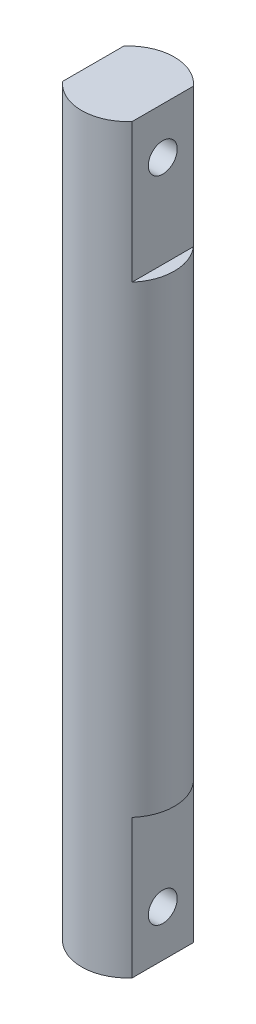
SolidWorks part; units mm, degrees
ref_plane "前视基准面" through (0, 0, 0) normal (0, 0, 1) x (1, 0, 0)
ref_plane "上视基准面" through (0, 0, 0) normal (0, 1, 0) x (1, 0, 0)
ref_plane "右视基准面" through (0, 0, 0) normal (1, 0, 0) x (0, 0, -1)
other "Configuration Table"
sketch "草图1" plane through (0, 0, 0) normal (0, 1, 0) x (1, 0, 0)
  circle A0 centre (0, 0) radius 4
  dimension "D1" = 8
extrude "凸台-拉伸1" add sketch "草图1" along normal blind 32 and the other way blind 32
ref_plane "基准面1" through (10, 0, 0) normal (1, 0, 0) x (0, 0, -1)
sketch "草图7" plane through (10, 0, 0) normal (1, 0, 0) x (0, 0, -1)
  circle A0 centre (0, 28) radius 1.25
  circle A1 centre (0, -28) radius 1.25
  dimension "D1" = 2.5
  dimension "D2" = 2.5
  dimension "D3" = 28
  dimension "D4" = 28
sketch "草图8" plane through (10, 0, 0) normal (1, 0, 0) x (0, 0, -1)
  line L1 (-12.0569, 37.3082) -> (15.3796, 37.3082)
  line L2 (-12.0569, 37.3082) -> (-12.0569, -37.8679)
  line L3 (-12.0569, -37.8679) -> (15.3796, -37.8679)
  line L4 (15.3796, 37.3082) -> (15.3796, -37.8679)
sketch "草图17" plane through (10, 0, 0) normal (1, 0, 0) x (0, 0, -1)
  point P0 (0, 28)
  point P3 (0, -28)
hole_wizard "M3 螺纹孔2" positions "草图17" profile "草图16" tap size "M3" standard "GB" end condition through all
sketch "草图16" plane through (10, 28, 0) normal (0, 1, 0) x (0, 0, -1)
  line L0 (0, 0) -> (0, 14)
  line L1 (0, 14) -> (1.25, 14)
  line L2 (1.25, 14) -> (1.25, 0.275)
  line L3 (1.25, 0.275) -> (1.525, 0)
  line L5 (1.525, 0) -> (0, 0)
  line L6 (-1.25, 0.275) -> (-1.525, 0) construction
  line L11 (0, -6.35) -> (0, 107.95) construction
  dimension "通孔螺纹孔钻头直径" = 2.5
  dimension "通孔螺纹孔钻头深度" = 14
  dimension "近端锥形沉头孔直径" = 3.05
  dimension "近端锥形沉头孔角度" = 90
cosmetic thread "孔螺纹线3" parameters "D2"=3
cosmetic thread "孔螺纹线4" parameters "D2"=3
sketch "草图18" plane through (10, 0, 0) normal (1, 0, 0) x (0, 0, -1)
  line L1 (-17.2448, 39.0552) -> (16.0059, 39.0552)
  line L2 (-17.2448, 39.0552) -> (-17.2448, 20)
  line L3 (-17.2448, 20) -> (16.0059, 20)
  line L4 (16.0059, 39.0552) -> (16.0059, 20)
  line L5 (-23.3195, -20) -> (22.784, -20)
  line L6 (-23.3195, -20) -> (-23.3195, -55.5527)
  line L7 (-23.3195, -55.5527) -> (22.784, -55.5527)
  line L8 (22.784, -20) -> (22.784, -55.5527)
  dimension "D1" = 20
  dimension "D2" = 20
extrude "切除-拉伸1" cut sketch "草图18" against normal blind 7
sketch "草图19" plane through (0, -32, 0) normal (0, -1, 0) x (1, 0, 0)
  line L0 (0, 0) -> (0, 2.7362) construction
  line L1 (3, -2.6458) -> (3, 2.6458) construction
  line L2 (3, -2.6458) -> (3, 2.6458)
  line L3 (-3, -2.6458) -> (-3, 2.6458)
  arc A0 (3, -2.6458) -> (3, 2.6458) centre (0, 0) ccw construction
  arc A1 (3, -2.6458) -> (3, 2.6458) centre (0, 0) ccw
  arc A2 (-3, -2.6458) -> (-3, 2.6458) centre (0, 0) cw
extrude "切除-拉伸2" cut sketch "草图19" against normal blind 12
sketch "草图20" plane through (0, 32, 0) normal (0, 1, 0) x (1, 0, 0)
  line L0 (0, 0) -> (0, 5.7593) construction
  line L1 (3, -2.6458) -> (3, 2.6458) construction
  line L2 (3, -2.6458) -> (3, 2.6458)
  line L3 (-3, -2.6458) -> (-3, 2.6458)
  arc A0 (3, -2.6458) -> (3, 2.6458) centre (0, 0) ccw construction
  arc A1 (3, -2.6458) -> (3, 2.6458) centre (0, 0) ccw
  arc A2 (-3, -2.6458) -> (-3, 2.6458) centre (0, 0) cw
extrude "切除-拉伸3" cut sketch "草图20" against normal blind 12
